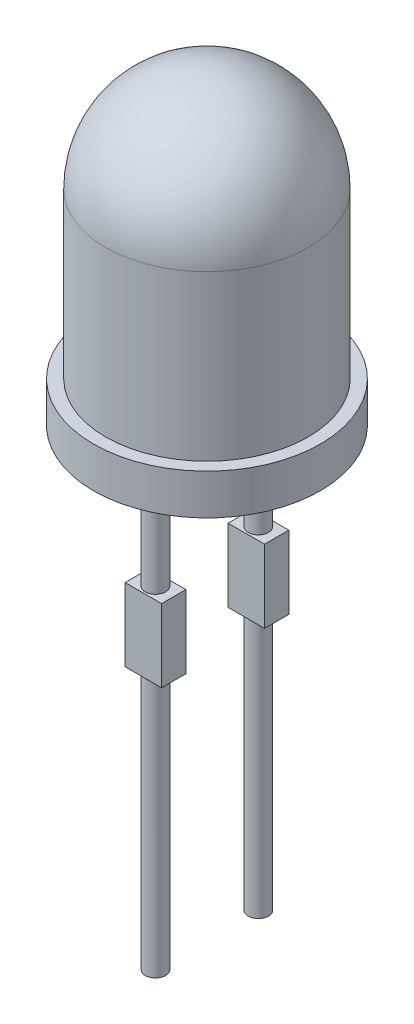
SolidWorks part; units mm, degrees
ref_plane "Front Plane" through (0, 0, 0) normal (0, 0, 1) x (1, 0, 0)
ref_plane "Top Plane" through (0, 0, 0) normal (0, 1, 0) x (1, 0, 0)
ref_plane "Right Plane" through (0, 0, 0) normal (1, 0, 0) x (0, 0, -1)
sketch "Sketch1" plane through (0, 0, 0) normal (1, 0, 0) x (0, 0, -1)
  line L0 (0, 4.525) -> (0, -10.9525) construction
  line L1 (-2.5, 2.025) -> (-2.5, -2.025)
  line L2 (-2.5, -2.025) -> (-2.8, -2.025)
  line L3 (-2.8, -2.025) -> (-2.8, -3.025)
  line L4 (-2.8, -3.025) -> (0, -3.025)
  line L5 (0, 4.525) -> (-4.2269, 4.525) construction
  line L6 (0, 4.525) -> (0, -3.025)
  arc A0 (-2.5, 2.025) -> (0, 4.525) centre (0, 2.025) cw
  point P11 (-2.5, 0)
  dimension "D1" = 5
  dimension "D2" = 7.55
  dimension "D3" = 1
  dimension "D4" = 5.6
revolve "Revolve1" add sketch "Sketch1" angle 360 about L0
sketch "Sketch2" plane through (0, -3.025, 0) normal (0, -1, 0) x (1, 0, 0)
  line L0 (0, 0) -> (3.908, 0) construction
  circle A0 centre (0, 1.27) radius 0.25
  circle A1 centre (0, -1.27) radius 0.25
  point P5 (0, 0)
  dimension "D1" = 2.54
  dimension "D2" = 0.5
extrude "Boss-Extrude1" add sketch "Sketch2" along normal blind 11 separate body
sketch "Sketch3" plane through (0, 0, 0) normal (1, 0, 0) x (0, 0, -1)
  line L0 (1.27, -3.025) -> (1.27, -15.6133) construction
  line L1 (0.97, -5.825) -> (1.57, -5.825)
  line L2 (0.97, -5.825) -> (0.97, -7.625)
  line L3 (0.97, -7.625) -> (1.57, -7.625)
  line L4 (1.57, -5.825) -> (1.57, -7.625)
  line L5 (0.97, -5.825) -> (1.57, -7.625) construction
  line L6 (0.97, -7.625) -> (1.57, -5.825) construction
  line L7 (1.52, -3.025) -> (1.02, -3.025) construction
  line L8 (-2.8, -3.025) -> (2.8, -3.025) construction
  line L9 (0, 0) -> (0, -3.6509) construction
  line L10 (-0.97, -7.625) -> (-1.57, -7.625)
  line L11 (-1.57, -5.825) -> (-1.57, -7.625)
  line L12 (-0.97, -5.825) -> (-1.57, -5.825)
  line L13 (-0.97, -5.825) -> (-0.97, -7.625)
  point P0 (1.27, -6.725)
  dimension "D1" = 0.6
  dimension "D2" = 2.8
  dimension "D3" = 1.8
extrude "Boss-Extrude2" add sketch "Sketch3" along normal mid plane 0.9
